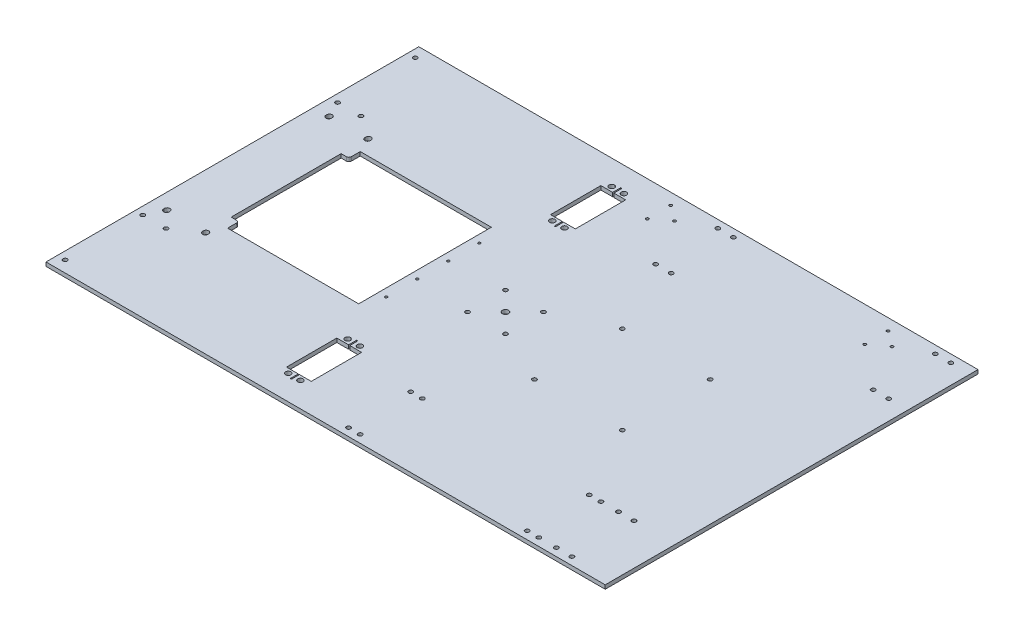
SolidWorks part; units mm, degrees
ref_plane "Front Plane" through (0, 0, 0) normal (0, 0, 1) x (1, 0, 0)
ref_plane "Top Plane" through (0, 0, 0) normal (0, 1, 0) x (1, 0, 0)
ref_plane "Right Plane" through (0, 0, 0) normal (1, 0, 0) x (0, 0, -1)
sketch "Sketch1" plane through (0, 0, 0) normal (0, 1, 0) x (1, 0, 0)
  line L1 (-228.6, -152.4) -> (228.6, -152.4)
  line L2 (-228.6, -152.4) -> (-228.6, 152.4)
  line L3 (-228.6, 152.4) -> (228.6, 152.4)
  line L4 (228.6, -152.4) -> (228.6, 152.4)
  line L5 (-228.6, -152.4) -> (228.6, 152.4) construction
  line L6 (-228.6, 152.4) -> (228.6, -152.4) construction
  point P0 (0, 0)
  dimension "D1" = 304.8
  dimension "D2" = 457.2
extrude "Boss-Extrude1" add sketch "Sketch1" along normal blind 3.175 contours L3 L4 L1 L2
sketch "Sketch2" plane through (0, 3.175, 0) normal (0, 1, 0) x (1, 0, 0)
  line L0 (-215.9, 66.04) -> (-215.9, 66.675) construction
  line L1 (-218.1, 66.04) -> (-218.1, 66.675)
  line L2 (-213.7, 66.04) -> (-213.7, 66.675)
  line L3 (-184.15, 66.04) -> (-184.15, 66.675) construction
  line L4 (-186.35, 66.04) -> (-186.35, 66.675)
  line L5 (-181.95, 66.04) -> (-181.95, 66.675)
  line L6 (-215.9, -66.04) -> (-215.9, -66.675) construction
  line L7 (-213.7, -66.04) -> (-213.7, -66.675)
  line L8 (-218.1, -66.04) -> (-218.1, -66.675)
  line L9 (-184.15, -66.04) -> (-184.15, -66.675) construction
  line L10 (-181.95, -66.04) -> (-181.95, -66.675)
  line L11 (-186.35, -66.04) -> (-186.35, -66.675)
  circle A0 centre (-184.15, -66.675) radius 2.2 construction
  circle A1 centre (-215.9, -66.675) radius 2.2 construction
  circle A2 centre (-184.15, 66.675) radius 2.2 construction
  circle A3 centre (-215.9, 66.675) radius 2.2 construction
  circle A6 centre (-184.15, -66.675) radius 2.2 construction
  circle A7 centre (-215.9, -66.675) radius 2.2 construction
  circle A8 centre (-184.15, 66.675) radius 2.2 construction
  circle A9 centre (-215.9, 66.675) radius 2.2 construction
  arc A10 (-218.1, 66.04) -> (-213.7, 66.04) centre (-215.9, 66.04) ccw
  arc A11 (-213.7, 66.675) -> (-218.1, 66.675) centre (-215.9, 66.675) ccw
  arc A12 (-186.35, 66.04) -> (-181.95, 66.04) centre (-184.15, 66.04) ccw
  arc A13 (-181.95, 66.675) -> (-186.35, 66.675) centre (-184.15, 66.675) ccw
  arc A14 (-213.7, -66.04) -> (-218.1, -66.04) centre (-215.9, -66.04) ccw
  arc A15 (-218.1, -66.675) -> (-213.7, -66.675) centre (-215.9, -66.675) ccw
  arc A16 (-181.95, -66.04) -> (-186.35, -66.04) centre (-184.15, -66.04) ccw
  arc A17 (-186.35, -66.675) -> (-181.95, -66.675) centre (-184.15, -66.675) ccw
  point P9 (-215.9, 66.3575)
  point P19 (-184.15, 66.3575)
  point P25 (-215.9, -66.3575)
  point P30 (-184.15, -66.3575)
  point P36 (0, 0)
  dimension "D1" = 0.635
extrude "Cut-Extrude1" cut sketch "Sketch2" against normal through all
sketch "Sketch3" plane through (0, 3.175, 0) normal (0, 1, 0) x (1, 0, 0)
  line L0 (-228.6, 0) -> (228.6, 0) construction
  line L1 (-228.6, -152.4) -> (-228.6, 152.4) construction
  line L2 (228.6, -152.4) -> (228.6, 152.4) construction
sketch "Sketch4" plane through (0, 3.175, 0) normal (0, 1, 0) x (1, 0, 0)
  line L0 (-184.658, 44.958) -> (-184.658, -44.958)
  line L1 (-184.658, -44.958) -> (-180.34, -44.958)
  line L2 (-178.308, -46.99) -> (-178.308, -54.229)
  line L3 (-178.308, -54.229) -> (-71.12, -54.229)
  line L4 (-71.12, -54.229) -> (-71.12, 54.229)
  line L5 (-71.12, 54.229) -> (-178.308, 54.229)
  line L6 (-178.308, 54.229) -> (-178.308, 46.99)
  line L7 (-180.34, 44.958) -> (-184.658, 44.958)
  line L8 (-184.15, 44.45) -> (-184.15, -44.45)
  line L9 (-180.34, 44.45) -> (-184.15, 44.45)
  line L10 (-177.8, 53.721) -> (-177.8, 46.99)
  line L11 (-71.628, 53.721) -> (-177.8, 53.721)
  line L12 (-71.628, -53.721) -> (-71.628, 53.721)
  line L13 (-177.8, -53.721) -> (-71.628, -53.721)
  line L14 (-177.8, -46.99) -> (-177.8, -53.721)
  line L15 (-184.15, -44.45) -> (-180.34, -44.45)
  line L16 (-184.15, 44.45) -> (-184.15, -44.45) construction
  line L17 (-180.34, 44.45) -> (-184.15, 44.45) construction
  line L18 (-177.8, 53.721) -> (-177.8, 46.99) construction
  line L19 (-71.628, 53.721) -> (-177.8, 53.721) construction
  line L20 (-71.628, -53.721) -> (-71.628, 53.721) construction
  line L21 (-177.8, -53.721) -> (-71.628, -53.721) construction
  line L22 (-177.8, -46.99) -> (-177.8, -53.721) construction
  line L23 (-184.15, -44.45) -> (-180.34, -44.45) construction
  arc A0 (-178.308, -46.99) -> (-180.34, -44.958) centre (-180.34, -46.99) ccw
  arc A1 (-180.34, 44.958) -> (-178.308, 46.99) centre (-180.34, 46.99) ccw
  arc A2 (-180.34, 44.45) -> (-177.8, 46.99) centre (-180.34, 46.99) ccw
  arc A3 (-177.8, -46.99) -> (-180.34, -44.45) centre (-180.34, -46.99) ccw
  arc A4 (-180.34, 44.45) -> (-177.8, 46.99) centre (-180.34, 46.99) ccw construction
  arc A5 (-177.8, -46.99) -> (-180.34, -44.45) centre (-180.34, -46.99) ccw construction
  dimension "D2" = 0.508
extrude "Cut-Extrude2" cut sketch "Sketch4" against normal up to next
sketch "Sketch5" plane through (0, 3.175, 0) normal (0, 1, 0) x (1, 0, 0)
  circle A0 centre (-203.2, 79.629) radius 1.7 construction
  circle A1 centre (-222.25, 143.129) radius 1.7 construction
  circle A2 centre (-222.25, 79.629) radius 1.7 construction
  circle A3 centre (-203.2, -79.629) radius 1.7 construction
  circle A4 centre (-222.25, -79.629) radius 1.7 construction
  circle A5 centre (-222.25, -143.129) radius 1.7 construction
  circle A6 centre (-203.2, 79.629) radius 1.7
  circle A7 centre (-222.25, 143.129) radius 1.7
  circle A8 centre (-222.25, 79.629) radius 1.7
  circle A9 centre (-203.2, -79.629) radius 1.7
  circle A10 centre (-222.25, -79.629) radius 1.7
  circle A11 centre (-222.25, -143.129) radius 1.7
extrude "Cut-Extrude3" cut sketch "Sketch5" against normal through all
sketch "Sketch7" plane through (0, 3.175, 0) normal (0, 1, 0) x (1, 0, 0)
  line L0 (-55.847, -87.373) -> (-35.593, -128.527) construction
  line L1 (-55.847, -87.373) -> (-46.22, -87.373)
  line L2 (-55.847, -87.373) -> (-55.847, -128.527)
  line L3 (-55.847, -128.527) -> (-46.22, -128.527)
  line L4 (-35.593, -87.373) -> (-35.593, -128.527)
  line L5 (-35.593, -87.373) -> (-55.847, -128.527) construction
  line L6 (-50.72, -83.65) -> (-40.72, -132.25) construction
  line L7 (-50.72, -132.25) -> (-40.72, -83.65) construction
  line L9 (-228.6, -152.4) -> (228.6, -152.4) construction
  line L10 (-45.22, -128.527) -> (-35.593, -128.527)
  line L12 (-46.22, -128.527) -> (-46.22, -135.131)
  line L13 (-46.22, -135.131) -> (-45.22, -135.131)
  line L14 (-45.22, -128.527) -> (-45.22, -135.131)
  line L15 (-45.72, -107.95) -> (-2.6371, -107.95) construction
  line L16 (-46.22, -80.769) -> (-45.22, -80.769)
  line L17 (-46.22, -87.373) -> (-46.22, -80.769)
  line L18 (-45.22, -87.373) -> (-45.22, -80.769)
  line L19 (-45.22, -87.373) -> (-35.593, -87.373)
  line L20 (-228.6, -152.4) -> (-228.6, 152.4) construction
  circle A0 centre (-50.72, -132.25) radius 2.2
  circle A1 centre (-40.72, -132.25) radius 2.2
  circle A2 centre (-50.72, -83.65) radius 2.2
  circle A3 centre (-40.72, -83.65) radius 2.2
  point P8 (-45.72, -135.131)
  point P17 (-45.72, -107.95)
  point P18 (-45.72, -107.95)
  dimension "D5" = 4.4
  dimension "D2" = 10
  dimension "D4" = 48.6
  dimension "D1" = 41.154
  dimension "D3" = 20.254
  dimension "D6" = 44.45
  dimension "D7" = 1
  dimension "D8" = 6.604
  dimension "D9" = 182.88
extrude "Cut-Extrude5" cut sketch "Sketch7" against normal through all
mirror "Mirror1" about plane through (0, 0, 0) normal (0, 0, 1) of "Cut-Extrude5"
sketch "Sketch8" plane through (0, 3.175, 0) normal (0, 1, 0) x (1, 0, 0)
  circle A1 centre (-64.77, -38.1) radius 1
  circle A2 centre (-64.77, -38.1) radius 1
  circle A3 centre (-64.77, -12.7) radius 1
  circle A4 centre (-64.77, -12.7) radius 1
  circle A5 centre (-64.77, 12.7) radius 1
  circle A6 centre (-64.77, 12.7) radius 1
  circle A7 centre (-64.77, 38.1) radius 1
  circle A8 centre (-64.77, 38.1) radius 1
  dimension "D1" = 0
  dimension "D2" = 0
  dimension "D3" = 0
  dimension "D4" = 0
extrude "Cut-Extrude6" cut sketch "Sketch8" against normal through all
sketch "Sketch12" plane through (0, 3.175, 0) normal (0, 1, 0) x (1, 0, 0)
  circle A0 centre (195.024, -95.25) radius 1.7 construction
  circle A1 centre (182.324, -95.25) radius 1.7 construction
  circle A2 centre (195.024, -146.05) radius 1.7 construction
  circle A3 centre (182.324, -146.05) radius 1.7 construction
  circle A4 centre (167.9575, -95.25) radius 1.7 construction
  circle A5 centre (158.4325, -95.25) radius 1.7 construction
  circle A6 centre (167.9575, -146.05) radius 1.7 construction
  circle A7 centre (158.4325, -146.05) radius 1.7 construction
  circle A8 centre (21.9075, -146.05) radius 1.7 construction
  circle A9 centre (12.3825, -146.05) radius 1.7 construction
  circle A10 centre (12.3825, -95.25) radius 1.7 construction
  circle A11 centre (21.9075, -95.25) radius 1.7 construction
  circle A12 centre (195.024, -95.25) radius 1.7
  circle A13 centre (182.324, -95.25) radius 1.7
  circle A14 centre (195.024, -146.05) radius 1.7
  circle A15 centre (182.324, -146.05) radius 1.7
  circle A16 centre (167.9575, -95.25) radius 1.7
  circle A17 centre (158.4325, -95.25) radius 1.7
  circle A18 centre (167.9575, -146.05) radius 1.7
  circle A19 centre (158.4325, -146.05) radius 1.7
  circle A20 centre (21.9075, -146.05) radius 1.7
  circle A21 centre (12.3825, -146.05) radius 1.7
  circle A22 centre (12.3825, -95.25) radius 1.7
  circle A23 centre (21.9075, -95.25) radius 1.7
extrude "Cut-Extrude7" cut sketch "Sketch12" against normal through all
sketch "Sketch13" plane through (0, 3.175, 0) normal (0, 1, 0) x (1, 0, 0)
  circle A1 centre (212.725, 95.25) radius 1.7
  circle A2 centre (212.725, 95.25) radius 1.7
  circle A3 centre (212.725, 146.05) radius 1.7
  circle A4 centre (212.725, 146.05) radius 1.7
  circle A5 centre (200.025, 95.25) radius 1.7
  circle A6 centre (200.025, 95.25) radius 1.7
  circle A7 centre (200.025, 146.05) radius 1.7
  circle A8 centre (200.025, 146.05) radius 1.7
  circle A9 centre (177.213, 133.477) radius 1.127
  circle A10 centre (177.213, 133.477) radius 1.127
  circle A11 centre (164.513, 143.002) radius 1.127
  circle A12 centre (164.513, 143.002) radius 1.127
  circle A13 centre (164.513, 123.952) radius 1.127
  circle A14 centre (164.513, 123.952) radius 1.127
  circle A15 centre (34.925, 95.25) radius 1.7
  circle A16 centre (34.925, 95.25) radius 1.7
  circle A17 centre (34.925, 146.05) radius 1.7
  circle A18 centre (34.925, 146.05) radius 1.7
  circle A19 centre (22.225, 95.25) radius 1.7
  circle A20 centre (22.225, 95.25) radius 1.7
  circle A21 centre (22.225, 146.05) radius 1.7
  circle A22 centre (22.225, 146.05) radius 1.7
  circle A23 centre (-0.587, 133.477) radius 1.127
  circle A24 centre (-0.587, 133.477) radius 1.127
  circle A25 centre (-13.287, 143.002) radius 1.127
  circle A26 centre (-13.287, 143.002) radius 1.127
  circle A27 centre (-13.287, 123.952) radius 1.127
  circle A28 centre (-13.287, 123.952) radius 1.127
  dimension "D1" = 0
  dimension "D2" = 0
  dimension "D3" = 0
  dimension "D4" = 0
  dimension "D5" = 0
  dimension "D6" = 0
  dimension "D7" = 0
  dimension "D8" = 0
  dimension "D9" = 0
  dimension "D10" = 0
  dimension "D11" = 0
  dimension "D12" = 0
  dimension "D13" = 0
  dimension "D14" = 0
extrude "Cut-Extrude8" cut sketch "Sketch13" against normal through all
sketch "Sketch14" plane through (0, 3.175, 0) normal (0, 1, 0) x (1, 0, 0)
  line L0 (-20.834, -15.5) -> (10.166, -15.5) construction
  line L1 (54.249, -35.921) -> (126.091, -35.921) construction
  line L2 (54.249, -35.921) -> (54.249, 35.921) construction
  line L3 (54.249, 35.921) -> (126.091, 35.921) construction
  line L4 (126.091, -35.921) -> (126.091, 35.921) construction
  line L5 (54.249, -35.921) -> (126.091, 35.921) construction
  line L6 (54.249, 35.921) -> (126.091, -35.921) construction
  line L7 (-20.834, -15.5) -> (-20.834, 15.5) construction
  line L8 (-20.834, 15.5) -> (10.166, 15.5) construction
  line L9 (10.166, -15.5) -> (10.166, 15.5) construction
  line L10 (-20.834, -15.5) -> (10.166, 15.5) construction
  line L11 (-20.834, 15.5) -> (10.166, -15.5) construction
  circle A0 centre (90.17, 0) radius 9.525 construction
  circle A1 centre (-5.334, 0) radius 2.6035 construction
  circle A2 centre (90.17, 0) radius 9.525 construction
  circle A3 centre (-5.334, 0) radius 2.6035 construction
  circle A4 centre (54.249, 35.921) radius 1.7
  circle A5 centre (126.091, 35.921) radius 1.7
  circle A7 centre (54.249, -35.921) radius 1.7
  circle A9 centre (126.091, -35.921) radius 1.7
  circle A12 centre (-20.834, 15.5) radius 1.7
  circle A13 centre (10.166, 15.5) radius 1.7
  circle A14 centre (-20.834, -15.5) radius 1.7
  circle A15 centre (10.166, -15.5) radius 1.7
  circle A16 centre (-5.334, 0) radius 2.5
  point P26 (0, 0)
  point P29 (0, 0)
  point P30 (0, 0)
  dimension "D2" = 3.4
  dimension "D5" = 3.4
  dimension "D6" = 5
  dimension "D4" = 31
  dimension "D1" = 101.6
extrude "Cut-Extrude9" cut sketch "Sketch14" against normal through all
equation "\"tightTol\"= 0.005in"
equation "\"normTol\"= 0.01in"
equation "\"looseTol\"= 0.02in"
equation "\"D2@Sketch4\"=\"looseTol\""
equation "\"D2@Sketch14\"=3.4mm"
equation "\"D5@Sketch7\"=4.4mm"
